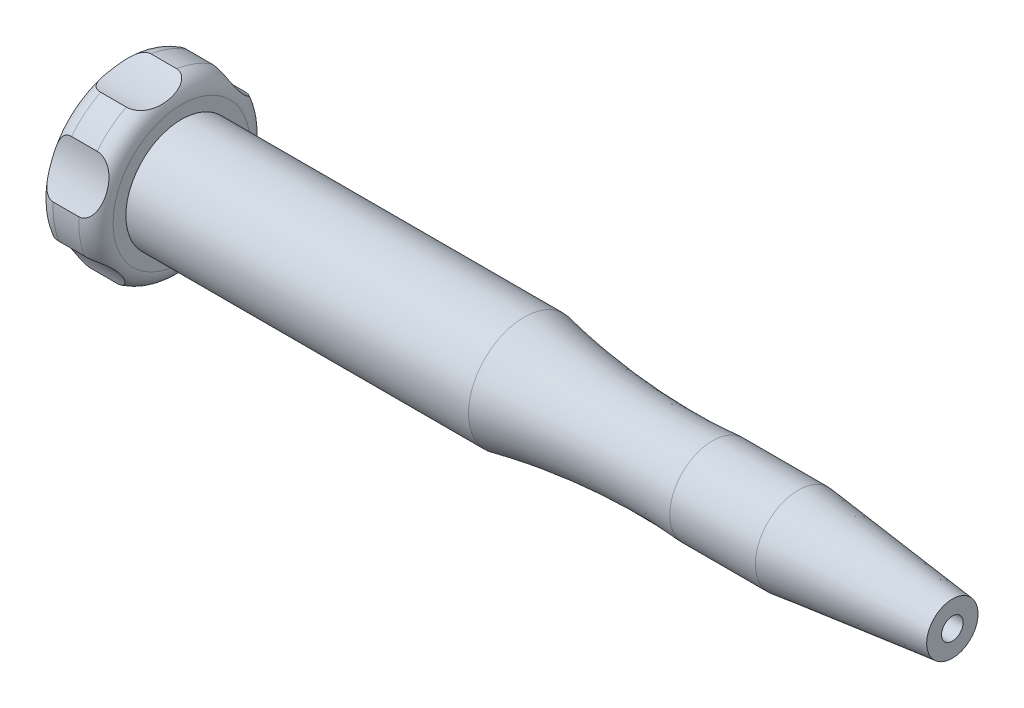
SolidWorks part; units mm, degrees
ref_plane "Front Plane" through (0, 0, 0) normal (0, 0, 1) x (1, 0, 0)
ref_plane "Top Plane" through (0, 0, 0) normal (0, 1, 0) x (1, 0, 0)
ref_plane "Right Plane" through (0, 0, 0) normal (1, 0, 0) x (0, 0, -1)
sketch "Sketch1" plane through (0, 0, 0) normal (0, 0, 1) x (1, 0, 0)
  line L0 (0, 0) -> (-50.4861, 0)
  line L2 (-50.0187, 10) -> (-47.0188, 10)
  line L3 (-45.0187, 8) -> (-45.0187, 6.5)
  line L4 (-45.0187, 6.5) -> (-5.0187, 6.5)
  line L6 (16.9813, 5) -> (26.9813, 5)
  line L7 (26.9813, 5) -> (44.9813, 3)
  line L8 (44.9813, 3) -> (44.9813, 0)
  line L9 (44.9813, 0) -> (0, 0)
  line L10 (-50.4861, 0) -> (61.6223, 0) construction
  arc A0 (-52.0187, 8) -> (-50.0187, 10) centre (-50.0187, 8) cw
  arc A1 (-47.0188, 10) -> (-45.0187, 8) centre (-47.0187, 8) cw
  spline S0 degree 2 poles (-5.0187, 6.5) (5.8787, 4.2482) (16.9813, 5) knots 0 0 0 1 1 1
  spline S1 degree 2 poles (-52.0187, 8) (-50.1604, 4.2035) (-50.4861, 0) knots 0 0 0 1 1 1
  point P3 (0, 0)
  point P14 (-52.0178, 9.882)
  point P17 (-45.0187, 10)
  point P20 (-50.6789, 3.9543)
  dimension "D10" = 2
  dimension "D1" = 7
  dimension "D2" = 10
  dimension "D3" = 40
  dimension "D4" = 22
  dimension "D5" = 10
  dimension "D6" = 18
  dimension "D7" = 6.5
  dimension "D8" = 5
  dimension "D9" = 3
revolve "Revolve1" add sketch "Sketch1" angle 360 about L10
sketch "Sketch2" plane through (44.9813, 0, 0) normal (1, 0, 0) x (0, 0, -1)
  line L0 (-1.0699, -0.675) -> (1.0699, -0.675)
  line L1 (-1.0699, 0.675) -> (1.0699, 0.675)
  circle A0 centre (0, 0) radius 1.265
  dimension "D1" = 2.53
  dimension "D2" = 1.35
  dimension "D3" = 0.675
extrude "Cut-Extrude1" cut sketch "Sketch2" against normal blind 14.33 contours L1 A0 | L0 A0 | L1 A0 L0 region at (44.9813, 0, 0) region at (44.9813, -0.9165, 0) region at (44.9813, 0.9165, 0)
extrude "Cut-Extrude2" cut sketch "Sketch2<3>" against normal blind 3.12 from surface contours L1 A0 L0 region at (44.9813, 0, 0) starting at face at (30.6513, 0, -1.265)
sketch "Sketch2<3>" plane through (44.9813, 0, 0) normal (1, 0, 0) x (0, 0, -1) same geometry as "Sketch2"
sketch "Sketch3" plane through (-45.0187, 0, 0) normal (1, 0, 0) x (0, 0, -1)
  circle A0 centre (16.7276, -6.4017) radius 8.879
extrude "Cut-Extrude3" cut sketch "Sketch3" against normal blind 10
pattern_circular "CirPattern1" count 6 over 360 about axis through (-50.0187, 0, 0) along (-1, 0, 0) of "Cut-Extrude3"
